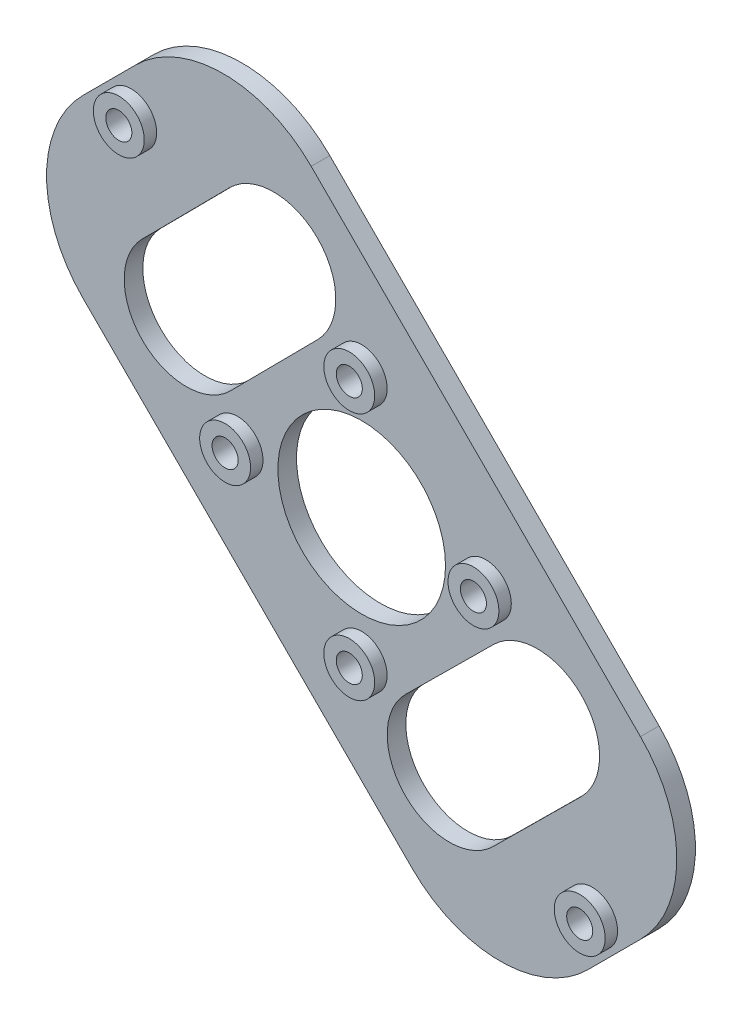
SolidWorks part; units mm, degrees
ref_plane "Plan de face" through (0, 0, 0) normal (0, 0, 1) x (1, 0, 0)
ref_plane "Plan de dessus" through (0, 0, 0) normal (0, 1, 0) x (1, 0, 0)
ref_plane "Plan de droite" through (0, 0, 0) normal (1, 0, 0) x (0, 0, -1)
sketch "Esquisse1" plane through (0, 0, 0) normal (0, 0, 1) x (1, 0, 0)
  line L0 (0, 0) -> (-40.6586, 40.6586) construction
  line L1 (0, 0) -> (0, 20) construction
  line L2 (22.2739, -59.0434) -> (-59.0434, 22.2739)
  line L3 (22.2739, -59.0434) -> (59.0434, -22.2739)
  line L4 (-59.0434, 22.2739) -> (-22.2739, 59.0434)
  line L5 (59.0434, -22.2739) -> (-22.2739, 59.0434)
  line L6 (22.2739, -59.0434) -> (-22.2739, 59.0434) construction
  line L7 (-59.0434, 22.2739) -> (59.0434, -22.2739) construction
  circle A0 centre (0, 0) radius 20 construction
  circle A1 centre (0, 20) radius 2.1
  circle A2 centre (0, 0) radius 13.5
  circle A3 centre (20, 0) radius 2.1
  circle A4 centre (0, -20) radius 2.1
  circle A5 centre (-20, 0) radius 2.1
  point P6 (-28.6465, 58.3096)
  point P15 (0, 0)
  point P19 (-40.6586, 40.6586)
  dimension "D1" = 40
  dimension "D2" = 4.2
  dimension "D3" = 27
  dimension "D5" = 45
  dimension "D6" = 52
  dimension "D7" = 115
  dimension "D4" = 4
extrude "Boss.-Extru.1" add sketch "Esquisse1" along normal blind 3
sketch "Esquisse2" plane through (0, 0, 3) normal (0, 0, 1) x (1, 0, 0)
  line L0 (-40.6586, 40.6586) -> (40.6586, -40.6586) construction
  line L1 (-22.2739, 59.0434) -> (-59.0434, 22.2739) construction
  line L2 (22.2739, -59.0434) -> (59.0434, -22.2739) construction
  line L3 (0, 0) -> (18.3848, 18.3848) construction
  line L4 (59.0434, -22.2739) -> (-22.2739, 59.0434) construction
  circle A0 centre (-37.1231, 37.1231) radius 2.1
  circle A1 centre (37.1231, -37.1231) radius 2.1
  dimension "D1" = 4.2
  dimension "D2" = 5
extrude "Enlèv. mat.-Extru.1" cut sketch "Esquisse2" against normal blind 3
sketch "Esquisse3" plane through (0, 0, 3) normal (0, 0, 1) x (1, 0, 0)
  circle A0 centre (37.1231, -37.1231) radius 2.1 construction
  circle A1 centre (20, 0) radius 2.1 construction
  circle A2 centre (0, -20) radius 2.1 construction
  circle A3 centre (-20, 0) radius 2.1 construction
  circle A4 centre (-37.1231, 37.1231) radius 2.1 construction
  circle A5 centre (0, 20) radius 2.1 construction
  circle A6 centre (37.1231, -37.1231) radius 2.1
  circle A7 centre (20, 0) radius 2.1
  circle A8 centre (0, -20) radius 2.1
  circle A9 centre (-20, 0) radius 2.1
  circle A10 centre (-37.1231, 37.1231) radius 2.1
  circle A11 centre (0, 20) radius 2.1
  circle A12 centre (37.1231, -37.1231) radius 4.1
  circle A13 centre (20, 0) radius 4.1
  circle A14 centre (0, -20) radius 4.1
  circle A15 centre (-20, 0) radius 4.1
  circle A16 centre (-37.1231, 37.1231) radius 4.1
  circle A17 centre (0, 20) radius 4.1
  dimension "D1" = 2
extrude "Boss.-Extru.2" add sketch "Esquisse3" along normal blind 2
sketch "Esquisse4" plane through (0, 0, 3) normal (0, 0, 1) x (1, 0, 0)
  line L0 (40.6586, -40.6586) -> (-40.6586, 40.6586) construction
  line L1 (-22.2739, 59.0434) -> (-59.0434, 22.2739) construction
  line L2 (-28.2522, 14.1102) -> (-14.1742, 28.3162) construction
  line L3 (-35.3552, 21.1492) -> (-21.2772, 35.3552)
  line L4 (-21.1492, 7.0712) -> (-7.0712, 21.2772)
  line L5 (0, 0) -> (18.3848, 18.3848) construction
  line L6 (59.0434, -22.2739) -> (-22.2739, 59.0434) construction
  line L7 (14.1102, -28.2522) -> (28.3162, -14.1742) construction
  line L8 (21.1492, -35.3552) -> (35.3552, -21.2772)
  line L9 (7.0712, -21.1492) -> (21.2772, -7.0712)
  arc A0 (-35.3552, 21.1492) -> (-21.1492, 7.0712) centre (-28.2522, 14.1102) ccw
  arc A1 (-7.0712, 21.2772) -> (-21.2772, 35.3552) centre (-14.1742, 28.3162) ccw
  arc A2 (21.1492, -35.3552) -> (7.0712, -21.1492) centre (14.1102, -28.2522) cw
  arc A3 (21.2772, -7.0712) -> (35.3552, -21.2772) centre (28.3162, -14.1742) cw
  point P7 (-21.2132, 21.2132)
  point P17 (21.2132, -21.2132)
  dimension "D1" = 10
  dimension "D2" = 20
  dimension "D3" = 30
extrude "Enlèv. mat.-Extru.2" cut sketch "Esquisse4" against normal blind 3
fillet "Congé1" radius 20 4 edges at (22.2739, -59.0434, 1.5) (59.0434, -22.2739, 1.5) (-22.2739, 59.0434, 1.5) (-59.0434, 22.2739, 1.5)
